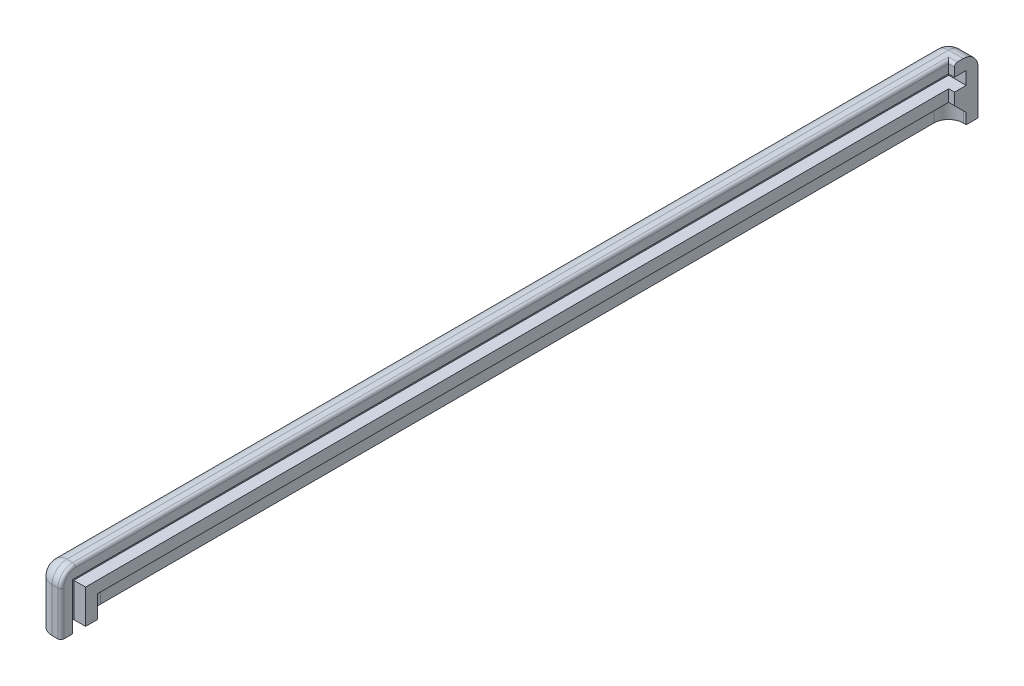
SolidWorks part; units mm, degrees
ref_plane "Front Plane" through (0, 0, 0) normal (0, 0, 1) x (1, 0, 0)
ref_plane "Top Plane" through (0, 0, 0) normal (0, 1, 0) x (1, 0, 0)
ref_plane "Right Plane" through (0, 0, 0) normal (1, 0, 0) x (0, 0, -1)
sketch "Sketch1" plane through (0, 0, 0) normal (0, 1, 0) x (1, 0, 0)
  line L1 (-19.5, 77.5) -> (19.5, 77.5)
  line L2 (-19.5, 77.5) -> (-19.5, -77.5)
  line L3 (-19.5, -77.5) -> (19.5, -77.5)
  line L4 (19.5, 77.5) -> (19.5, -77.5)
  line L5 (-19.5, 77.5) -> (19.5, -77.5) construction
  line L6 (-19.5, -77.5) -> (19.5, 77.5) construction
  point P0 (0, 0)
  dimension "D1" = 39
  dimension "D2" = 155
extrude "Boss-Extrude1" add sketch "Sketch1" along normal blind 2
sketch "Sketch2" plane through (0, 2, 0) normal (0, 1, 0) x (1, 0, 0)
  line L0 (-17.5, -75.5) -> (-17.5, -77.5)
  line L1 (-19.5, 77.5) -> (19.5, 77.5)
  line L2 (-19.5, 77.5) -> (-19.5, -77.5)
  line L3 (-19.5, -77.5) -> (19.5, -77.5)
  line L4 (19.5, 77.5) -> (19.5, -77.5)
  line L5 (-17.5, 75.5) -> (17.5, 75.5)
  line L6 (-17.5, 75.5) -> (-17.5, -75.5)
  line L7 (-17.5, -75.5) -> (17.5, -75.5)
  line L8 (17.5, 75.5) -> (17.5, -75.5)
  line L9 (-17.5, 75.5) -> (17.5, -75.5) construction
  line L10 (-17.5, -75.5) -> (17.5, 75.5) construction
  line L11 (17.5, -75.5) -> (17.5, -77.5)
  point P6 (0, 0)
  line M9 (19.5, -77.5) -> (19.5, 77.5)
  line M10 (19.5, 77.5) -> (-19.5, 77.5)
  line M11 (-19.5, 77.5) -> (-19.5, -77.5)
  line M12 (-19.5, -77.5) -> (19.5, -77.5)
  dimension "D1" = 2
  dimension "D2" = 2
extrude "Boss-Extrude2" add sketch "Sketch2" along normal blind 38 contours L8 L11 L3 L0 L6 L5 M9 M10 M11 M12 region at (-19.0983, 2, 76.5)
sketch "Sketch3" plane through (0, 2, 0) normal (0, 1, 0) x (1, 0, 0)
  line L0 (-17.5, 75.5) -> (-17.5, -77.5) construction
  line L1 (-17.5, -77.5) -> (-15.5, -77.5)
  line L2 (-17.5, -77.5) -> (-17.5, -75.5)
  line L3 (-17.5, -75.5) -> (-15.5, -75.5)
  line L4 (-15.5, -77.5) -> (-15.5, -75.5)
  line L5 (-17.5, -73.3) -> (-15.5, -73.3)
  line L6 (-17.5, -73.3) -> (-17.5, -71.3)
  line L7 (-17.5, -71.3) -> (-15.5, -71.3)
  line L8 (-15.5, -73.3) -> (-15.5, -71.3)
  line L9 (17.5, 75.5) -> (17.5, -77.5) construction
  line L10 (17.5, -77.5) -> (15.5, -77.5)
  line L11 (17.5, -77.5) -> (17.5, -75.5)
  line L12 (17.5, -75.5) -> (15.5, -75.5)
  line L13 (15.5, -77.5) -> (15.5, -75.5)
  line L14 (17.5, -73.3) -> (15.5, -73.3)
  line L15 (17.5, -73.3) -> (17.5, -71.3)
  line L16 (17.5, -71.3) -> (15.5, -71.3)
  line L17 (15.5, -73.3) -> (15.5, -71.3)
  line L18 (15.5, -75.5) -> (15.5, -73.3) construction
  line L19 (-15.5, -73.3) -> (15.5, -73.3) construction
  line L20 (-15.5, -75.5) -> (-15.5, -73.3) construction
  line L21 (-15.5, -75.5) -> (15.5, -75.5) construction
  line L22 (15.5, -71.3) -> (-15.5, -71.3) construction
  dimension "D1" = 2
  dimension "D2" = 2
  dimension "D3" = 2.2
  dimension "D4" = 2
extrude "Boss-Extrude3" add sketch "Sketch3" along normal up to surface (38 mm away) up to face at (0, 40, 0.5)
sketch "Sketch4" plane through (0, 0, -75.5) normal (0, 0, 1) x (1, 0, 0)
  line L0 (-17.5, 40) -> (-15.5, 40)
  line L1 (-17.5, 40) -> (17.5, 40) construction
  line L2 (-15.5, 40) -> (-15.5, 38)
  line L3 (-15.5, 38) -> (-17.5, 38)
  line L5 (-17.5, 38) -> (-17.5, 40)
  line L7 (-17.5, 40) -> (-17.5, 2) construction
  line L8 (-15.5, 33.8) -> (-17.5, 31.8)
  line L9 (-17.5, 31.8) -> (-17.5, 35.8)
  line L10 (-15.5, 33.8) -> (-15.5, 35.8)
  line L11 (-15.5, 35.8) -> (-17.5, 35.8)
  line L12 (0, 0) -> (0, 40) construction
  line L13 (15.5, 35.8) -> (17.5, 35.8)
  line L14 (15.5, 33.8) -> (15.5, 35.8)
  line L15 (17.5, 31.8) -> (17.5, 35.8)
  line L16 (15.5, 33.8) -> (17.5, 31.8)
  line L17 (17.5, 38) -> (17.5, 40)
  line L18 (15.5, 38) -> (17.5, 38)
  line L19 (15.5, 40) -> (15.5, 38)
  line L20 (17.5, 40) -> (15.5, 40)
  dimension "D1" = 2
  dimension "D2" = 2
  dimension "D3" = 45
  dimension "D4" = 2.2
  dimension "D5" = 2
extrude "Boss-Extrude4" add sketch "Sketch4" along normal up to surface (153 mm away) up to face at (0, 20.5, 77.5)
sketch "Sketch5" plane through (0, 2, 0) normal (0, 1, 0) x (1, 0, 0)
  line L1 (-15.5, -77.5) -> (15.5, -77.5)
  line L2 (-15.5, -77.5) -> (-15.5, -75.5)
  line L3 (-15.5, -75.5) -> (15.5, -75.5)
  line L4 (15.5, -77.5) -> (15.5, -75.5)
  line L5 (-15.5, -71.3) -> (15.5, -71.3)
  line L6 (-15.5, -71.3) -> (-15.5, -73.3)
  line L7 (-15.5, -73.3) -> (15.5, -73.3)
  line L8 (15.5, -71.3) -> (15.5, -73.3)
sketch "Sketch6" plane through (0, 0, -75.5) normal (0, 0, 1) x (1, 0, 0)
  line L0 (-17.5, 38) -> (-15.5, 38) construction
  line L1 (-17.5, 38) -> (17.5, 38)
  line L2 (-17.5, 38) -> (-17.5, 35.8)
  line L3 (-17.5, 35.8) -> (17.5, 35.8)
  line L4 (17.5, 38) -> (17.5, 35.8)
  line L5 (-17.5, 38) -> (-17.5, 35.8) construction
  line L6 (-15.5, 35.8) -> (-17.5, 35.8) construction
extrude "Cut-Extrude1" cut sketch "Sketch6" along normal through all
sketch "Sketch7" plane through (0, 2, 0) normal (0, 1, 0) x (1, 0, 0)
  line L1 (-17.5, -75.5) -> (17.5, -75.5)
  line L2 (-17.5, -75.5) -> (-17.5, -73.3)
  line L3 (-17.5, -73.3) -> (17.5, -73.3)
  line L4 (17.5, -75.5) -> (17.5, -73.3)
extrude "Cut-Extrude2" cut sketch "Sketch7" along normal through all
extrude "Boss-Extrude5" add sketch "Sketch5" along normal blind 2
sketch "Sketch8" plane through (0, 0, 0) normal (1, 0, 0) x (0, 0, -1)
  line L0 (75.5, 40) -> (73.5, 40)
  line L1 (-73.3, 40) -> (75.5, 40) construction
  line L2 (73.5, 40) -> (73.5, 38)
  line L3 (-73.3, 38) -> (75.5, 38) construction
  line L4 (73.5, 38) -> (75.5, 38)
  line L5 (75.5, 38) -> (75.5, 40)
  line L6 (75.5, 35.8) -> (73.5, 35.8)
  line L7 (-73.3, 35.8) -> (75.5, 35.8) construction
  line L8 (73.5, 35.8) -> (73.5, 33.8)
  line L9 (-71.3, 33.8) -> (75.5, 33.8) construction
  line L10 (73.5, 33.8) -> (75.5, 31.8)
  line L11 (75.5, 31.8) -> (75.5, 35.8)
  dimension "D1" = 2
extrude "Boss-Extrude6" add sketch "Sketch8" along normal up to surface and the other way up to surface up to face at (17.5, 16.9, -2.1) other way up to face at (-17.5, 16.9, -2.1)
sketch "Sketch10" plane through (-17.5, 0, 0) normal (1, 0, 0) x (0, 0, -1)
  line L1 (-75.5, 35.8) -> (-77.5, 35.8)
  line L2 (-75.5, 35.8) -> (-75.5, 38)
  line L3 (-75.5, 38) -> (-77.5, 38)
  line L4 (-77.5, 35.8) -> (-77.5, 38)
  line L5 (-73.3, 40) -> (-75.5, 40)
  line L6 (-73.3, 40) -> (-73.3, 38)
  line L7 (-73.3, 38) -> (-75.5, 38)
  line L8 (-75.5, 40) -> (-75.5, 38)
  line M1 (-75.5, 40) -> (-75.5, 38)
  line M2 (-75.5, 38) -> (-77.5, 38)
  line M3 (-77.5, 38) -> (-77.5, 35.8)
  line M4 (-77.5, 35.8) -> (-75.5, 35.8)
  line M11 (-73.3, 38) -> (-73.3, 40)
  line M12 (-73.3, 40) -> (-75.5, 40)
extrude "Boss-Extrude8" add sketch "Sketch10" along normal up to surface (2 mm away) contours L2 M4 M2 M3 | L7 M11 M12 M1 region at (-17.5, 39, 74.4) region at (-17.5, 36.9, 76.5) up to face at (-15.5, 39, -0.1)
sketch "Sketch11" plane through (17.5, 0, 0) normal (-1, 0, 0) x (0, 0, 1)
  line L1 (75.5, 35.8) -> (77.5, 35.8)
  line L2 (75.5, 35.8) -> (75.5, 38)
  line L3 (75.5, 38) -> (77.5, 38)
  line L4 (77.5, 35.8) -> (77.5, 38)
  line L5 (73.3, 40) -> (75.5, 40)
  line L6 (73.3, 40) -> (73.3, 38)
  line L7 (73.3, 38) -> (75.5, 38)
  line L8 (75.5, 40) -> (75.5, 38)
  line M2 (75.5, 35.8) -> (77.5, 35.8)
  line M3 (77.5, 35.8) -> (77.5, 38)
  line M4 (77.5, 38) -> (75.5, 38)
  line M5 (75.5, 38) -> (75.5, 40)
  line M6 (75.5, 40) -> (73.3, 40)
  line M7 (73.3, 40) -> (73.3, 38)
extrude "Boss-Extrude9" add sketch "Sketch11" along normal up to surface (2 mm away) contours L2 M2 M3 M4 | L7 M7 M5 M6 region at (17.5, 36.9, 76.5) region at (17.5, 39, 74.4) up to face at (15.5, 39, -0.1)
fillet "Fillet2" radius 2.5 17 edges at (-17.5, 16.9, 71.3) (17.5, 16.9, 71.3) (19.5, 20, 77.5) (-19.5, 20, 77.5) (-19.5, 20, -77.5) (-17.5, 16.9, -75.5) (17.5, 16.9, -75.5) (19.5, 20, -77.5) (-19.5, 40, 0) (0, 40, -77.5) (19.5, 40, 0) (0, 0, -77.5) (0, 0, 77.5) (-19.5, 0, 0) (19.5, 0, 0) (-17.5, 40, 77.5) (17.5, 40, 77.5)
sketch "Sketch13" plane through (0, 0, -77.5) normal (0, 0, -1) x (-1, 0, 0)
  line L0 (15.5, 37.5) -> (15.5, 4) construction
  line L1 (-15.5, 7) -> (15.5, 7)
  line L2 (-15.5, 7) -> (-15.5, 4)
  line L3 (-15.5, 4) -> (15.5, 4)
  line L4 (15.5, 7) -> (15.5, 4)
  dimension "D1" = 3
sketch "Sketch14" plane through (0, 0, -75.5) normal (0, 0, 1) x (1, 0, 0)
  line L1 (-18.25, 9) -> (18.25, 9)
  line L2 (-18.25, 9) -> (-18.25, 1.25)
  line L3 (-18.25, 1.25) -> (18.25, 1.25)
  line L4 (18.25, 9) -> (18.25, 1.25)
  line L5 (15.5, 7) -> (-15.5, 7) construction
  line L7 (17, 0) -> (17, 2.5) construction
  line L8 (19.5, 2.5) -> (17, 2.5) construction
  line L10 (-19.5, 2.5) -> (-17, 2.5) construction
  point P20 (17, 1.25)
  point P23 (18.25, 2.5)
  point P26 (-18.25, 2.5)
  dimension "D1" = 2
extrude "Boss-Extrude10" add sketch "Sketch14" along normal blind 2
extrude "Cut-Extrude4" cut sketch "Sketch13" against normal blind 2
fillet "Fillet3" radius 2 1 edges at (0, 9, -73.5)
fillet "Fillet4" radius 0.5 12 edges at (0, 4, -77.5) (0, 7, -77.5) (15.5, 7, -76.5) (15.5, 4, -76.5) (15.5, 5.5, -77.5) (-15.5, 4, -76.5) (-15.5, 7, -76.5) (-15.5, 5.5, -77.5) (0, 7, -75.5) (-15.5, 5.5, -75.5) (0, 4, -75.5) (15.5, 5.5, -75.5)
sketch "Sketch15" plane through (0, 0, 0) normal (0, -1, 0) x (1, 0, 0)
  line L0 (0, 77.5) -> (0, 0) construction
  line L1 (-17, 77.5) -> (17, 77.5) construction
  line L2 (0, 0) -> (0, -77.5) construction
  line L4 (17, -77.5) -> (-17, -77.5) construction
  circle A0 centre (0, 38.75) radius 5.1
  circle A1 centre (0, -38.75) radius 5.1
  dimension "D1" = 10.2
extrude "Cut-Extrude5" cut sketch "Sketch15" against normal through all
sketch "Sketch16" plane through (0, 2, 0) normal (0, 1, 0) x (1, 0, 0)
  circle A0 centre (0, 38.75) radius 7.1
  circle A1 centre (0, -38.75) radius 7.1
  circle A2 centre (0, 38.75) radius 5.1 construction
  dimension "D1" = 2
extrude "Boss-Extrude11" add sketch "Sketch16" along normal blind 1
fillet "Fillet5" radius 0.5 4 edges at (0, 2, 45.85) (0, 2, -31.65) (0, 3, 45.85) (0, 3, -31.65)
sketch "Sketch12" plane through (0, 0, -75.5) normal (0, 0, 1) x (1, 0, 0)
  line L0 (0, 0) -> (0, 40) construction
  line L1 (15.5, 40) -> (-15.5, 40) construction
  line L2 (0, 20) -> (-10, 20)
  line L3 (0, 20) -> (-9.0097, 15.6612)
  line L4 (0, 20) -> (-6.2349, 12.1817)
  line L5 (0, 20) -> (-2.2252, 10.2507)
  line L6 (0, 20) -> (2.2252, 10.2507)
  line L7 (0, 20) -> (6.2349, 12.1817)
  line L8 (0, 20) -> (9.0097, 15.6612)
  line L9 (0, 20) -> (10, 20)
  line L10 (0, 20) -> (9.0097, 24.3388)
  line L11 (0, 20) -> (6.2349, 27.8183)
  line L12 (0, 20) -> (2.2252, 29.7493)
  line L13 (0, 20) -> (-2.2252, 29.7493)
  line L14 (0, 20) -> (-6.2349, 27.8183)
  line L15 (0, 20) -> (-9.0097, 24.3388)
  circle A0 centre (0, 20) radius 10
  circle A1 centre (0, 20) radius 7.5
  circle A2 centre (0, 20) radius 5
  circle A3 centre (0, 20) radius 2.5
  point P26 (0, 20)
  dimension "D1" = 20
  dimension "D2" = 2.5
  dimension "D3" = 2.5
  dimension "D4" = 2.5
  dimension "D5" = 14
extrude "Cut-Extrude3" cut sketch "Sketch12" against normal through all contours A1 L6 A0 L7 | A1 L4 A0 L5 | A1 L2 A0 L3 | A1 L14 A0 L15 | A1 L0 A0 L13 | L0 A1 L12 A0 | A1 L10 A0 L11 | A1 L8 A0 L9 | A3 L8 A2 L9 | A3 L10 A2 L11 | L0 A3 L12 A2 | A3 L0 A2 L13 | A3 L14 A2 L15 | A3 L2 A2 L3 | A3 L4 A2 L5 | A3 L6 A2 L7 region at (-3.7903, 12.1293, -75.5) region at (3.7903, 12.1293, -75.5) region at (-1.6732, 16.5256, -75.5) region at (1.6732, 16.5256, -75.5) region at (-8.5168, 18.0561, -75.5) region at (8.5168, 18.0561, -75.5) region at (-0.4345, 23.8563, -75.5) region at (0.4345, 23.8563, -75.5) region at (-3.7596, 19.1419, -75.5) region at (3.7596, 19.1419, -75.5) region at (3.015, 22.4044, -75.5) region at (-3.015, 22.4044, -75.5) region at (-6.8299, 25.4467, -75.5) region at (6.8299, 25.4467, -75.5) region at (-0.9843, 28.7358, -75.5) region at (0.9843, 28.7358, -75.5)
fillet "Fillet6" radius 0.4 112 edges at (5.4555, 26.841, -77.5) (7.8183, 26.2349, -77.5) (7.8835, 23.7965, -77.5) (5.8637, 24.6762, -77.5) (3.75, 20, -77.5) (4.8746, 18.8874, -77.5) (3.3786, 18.3729, -77.5) (2.4373, 19.4437, -77.5) (-1.9471, 28.5306, -77.5) (0, 30, -77.5) (1.9471, 28.5306, -77.5) (0, 27.5, -77.5) (-7.8835, 16.2035, -77.5) (-9.7493, 17.7748, -77.5) (-8.75, 20, -77.5) (-7.312, 18.3311, -77.5) (2.3381, 17.0681, -77.5) (2.1694, 15.4952, -77.5) (0.8345, 16.344, -77.5) (1.0847, 17.7476, -77.5) (-0.8345, 16.344, -77.5) (-2.1694, 15.4952, -77.5) (-2.3381, 17.0681, -77.5) (-1.0847, 17.7476, -77.5) (5.4555, 13.159, -77.5) (4.3388, 10.9903, -77.5) (1.9471, 11.4694, -77.5) (3.2541, 13.2427, -77.5) (0, 22.5, -77.5) (-0.8345, 23.656, -77.5) (0, 25, -77.5) (0.8345, 23.656, -77.5) (-3.3786, 21.6271, -77.5) (-3.9092, 23.1174, -77.5) (-2.3381, 22.9319, -77.5) (-1.9546, 21.5587, -77.5) (-3.3786, 18.3729, -77.5) (-4.8746, 18.8874, -77.5) (-3.75, 20, -77.5) (-2.4373, 19.4437, -77.5) (-1.9471, 11.4694, -77.5) (-4.3388, 10.9903, -77.5) (-5.4555, 13.159, -77.5) (-3.2541, 13.2427, -77.5) (-7.8835, 23.7965, -77.5) (-7.8183, 26.2349, -77.5) (-5.4555, 26.841, -77.5) (-5.8637, 24.6762, -77.5) (2.3381, 22.9319, -77.5) (3.9092, 23.1174, -77.5) (3.3786, 21.6271, -77.5) (1.9546, 21.5587, -77.5) (8.75, 20, -77.5) (9.7493, 17.7748, -77.5) (7.8835, 16.2035, -77.5) (7.312, 18.3311, -77.5) (7.8835, 23.7965, -75.5) (7.8183, 26.2349, -75.5) (5.4555, 26.841, -75.5) (5.8637, 24.6762, -75.5) (3.3786, 18.3729, -75.5) (4.8746, 18.8874, -75.5) (3.75, 20, -75.5) (2.4373, 19.4437, -75.5) (1.9471, 28.5306, -75.5) (0, 30, -75.5) (-1.9471, 28.5306, -75.5) (0, 27.5, -75.5) (-8.75, 20, -75.5) (-9.7493, 17.7748, -75.5) (-7.8835, 16.2035, -75.5) (-7.312, 18.3311, -75.5) (0.8345, 16.344, -75.5) (2.1694, 15.4952, -75.5) (2.3381, 17.0681, -75.5) (1.0847, 17.7476, -75.5) (-2.3381, 17.0681, -75.5) (-2.1694, 15.4952, -75.5) (-0.8345, 16.344, -75.5) (-1.0847, 17.7476, -75.5) (1.9471, 11.4694, -75.5) (4.3388, 10.9903, -75.5) (5.4555, 13.159, -75.5) (3.2541, 13.2427, -75.5) (0, 22.5, -75.5) (0.8345, 23.656, -75.5) (0, 25, -75.5) (-0.8345, 23.656, -75.5) (-2.3381, 22.9319, -75.5) (-3.9092, 23.1174, -75.5) (-3.3786, 21.6271, -75.5) (-1.9546, 21.5587, -75.5) (-3.75, 20, -75.5) (-4.8746, 18.8874, -75.5) (-3.3786, 18.3729, -75.5) (-2.4373, 19.4437, -75.5) (-5.4555, 13.159, -75.5) (-4.3388, 10.9903, -75.5) (-1.9471, 11.4694, -75.5) (-3.2541, 13.2427, -75.5) (-5.4555, 26.841, -75.5) (-7.8183, 26.2349, -75.5) (-7.8835, 23.7965, -75.5) (-5.8637, 24.6762, -75.5) (3.3786, 21.6271, -75.5) (3.9092, 23.1174, -75.5) (2.3381, 22.9319, -75.5) (7.8835, 16.2035, -75.5) (9.7493, 17.7748, -75.5) (8.75, 20, -75.5) (7.312, 18.3311, -75.5) (1.9546, 21.5587, -75.5)
fillet "Fillet7" radius 0.5 8 edges at (15.5, 40, 0.75) (15.5, 39.2678, 76.7678) (-15.5, 40, 0.75) (-15.5, 39.2678, 76.7678) (0, 40, -73.5) (15.5, 20.75, 77.5) (-15.5, 20.75, 77.5) (0, 4, 77.5)
sketch "Sketch17" plane through (0, 0, 0) normal (0, -1, 0) x (1, 0, 0)
  line L0 (-17, -77.5) -> (-17, 70.3)
  line L1 (-17, -77.5) -> (17, -77.5)
  line L2 (17, -77.5) -> (17, 70.3)
  line L3 (17, -75) -> (17, 75) construction
  line L5 (17, 70.3) -> (15, 71.3)
  line L6 (15, 71.3) -> (15, 77.5)
  line L7 (15, 77.5) -> (-15, 77.5)
  line L8 (-15, 77.5) -> (-15, 71.3)
  line L9 (-15, 71.3) -> (-17, 70.3)
  line L10 (-17, 75) -> (-17, -75) construction
  line L12 (-15, 71.3) -> (15, 71.3) construction
  line L13 (17, 70.3) -> (-17, 70.3) construction
  line L14 (0, 71.3) -> (0, 77.5) construction
  line L15 (-17, 77.5) -> (17, 77.5) construction
  arc A0 (-19.5, -75) -> (-17, -77.5) centre (-17, -75) ccw construction
  dimension "D1" = 1
  dimension "D2" = 30
  dimension "D3" = 6.2
extrude "Cut-Extrude6" cut sketch "Sketch17" against normal blind 6
sketch "Sketch18" plane through (0, 0, 0) normal (0, 0, 1) x (1, 0, 0)
  line L0 (15, 9) -> (-15, 9) construction
  line L1 (-14.5, 9) -> (14.5, 9)
  line L2 (-14.5, 9) -> (-14.5, 6)
  line L3 (-14.5, 6) -> (14.5, 6)
  line L4 (14.5, 9) -> (14.5, 6)
  line L5 (-17, 6) -> (17, 6) construction
  line L6 (0, 6) -> (0, 0) construction
  dimension "D1" = 29
extrude "Cut-Extrude8" cut sketch "Sketch18" against normal through all
sketch "Sketch20" plane through (0, 0, 0) normal (0, 0, 1) x (1, 0, 0)
  line L0 (-16, 40) -> (16, 40) construction
  line L1 (-19.5, 40) -> (-14.5, 40)
  line L2 (-19.5, 40) -> (-19.5, 0)
  line L3 (-19.5, 0) -> (-14.5, 0)
  line L4 (-14.5, 40) -> (-14.5, 0)
  line L5 (-14.5, 6) -> (14.5, 6)
  line L6 (-14.5, 6) -> (-14.5, 40)
  line L7 (-14.5, 40) -> (14.5, 40)
  line L8 (14.5, 6) -> (14.5, 40)
  line L9 (14.5, 40) -> (19.5, 40)
  line L10 (14.5, 40) -> (14.5, 0)
  line L11 (14.5, 0) -> (19.5, 0)
  line L12 (19.5, 40) -> (19.5, 0)
  line L13 (-15, 0) -> (-17, 0) construction
  line L14 (-19.5, 2.5) -> (-19.5, 37.5) construction
  line L15 (17, 0) -> (15, 0) construction
  line L16 (19.5, 37.5) -> (19.5, 2.5) construction
extrude "Cut-Extrude11" cut sketch "Sketch20" against normal through all both and the other way through all contours L5 L8 L7 L4 | L12 L9 L8 L10 L11 region at (0, 23, 0) region at (17, 20, 0)
sketch "Sketch21" plane through (0, 0, 0) normal (1, 0, 0) x (0, 0, -1)
  line L0 (77.5, 37.5) -> (77.5, 7.5) construction
  line L1 (-77.5, 40) -> (77.5, 40)
  line L2 (-77.5, 40) -> (-77.5, 30)
  line L3 (-77.5, 30) -> (77.5, 30)
  line L4 (77.5, 40) -> (77.5, 30)
  line L5 (77.5, 30) -> (-77.5, 30)
  line L6 (77.5, 30) -> (77.5, 10)
  line L7 (77.5, 10) -> (-77.5, 10)
  line L8 (-77.5, 30) -> (-77.5, 10)
  line L9 (-77.5, 10) -> (77.5, 10)
  line L10 (-77.5, 10) -> (-77.5, 0)
  line L11 (-77.5, 0) -> (77.5, 0)
  line L12 (77.5, 10) -> (77.5, 0)
  line L13 (-70.3, 0) -> (75, 0) construction
  line L14 (-77.5, 3.5) -> (-77.5, 2.5) construction
  line L15 (-75, 40) -> (74, 40) construction
  line L16 (77.5, 30) -> (77.5, 10)
  line L17 (-77.5, 10) -> (-77.5, 30)
  dimension "D1" = 20
  dimension "D2" = 10
extrude "Cut-Extrude12" cut sketch "Sketch21" against normal through all contours L12 L7 L10 L11 | L3 L8 L7 L6 region at (0, 20, 0) region at (0, 5, 0)
